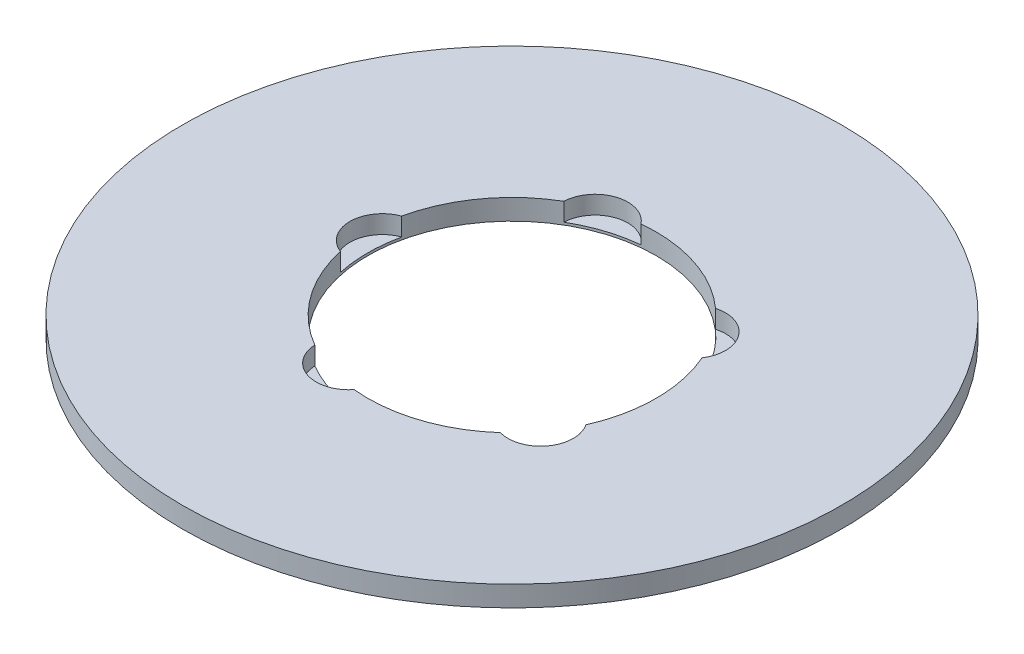
SolidWorks part; units mm, degrees
ref_plane "Front Plane" through (0, 0, 0) normal (0, 0, 1) x (1, 0, 0)
ref_plane "Top Plane" through (0, 0, 0) normal (0, 1, 0) x (1, 0, 0)
ref_plane "Right Plane" through (0, 0, 0) normal (1, 0, 0) x (0, 0, -1)
sketch "Sketch1" plane through (0, 0, 0) normal (0, 1, 0) x (1, 0, 0)
  circle A0 centre (0, 0) radius 80
  dimension "FLANGE_OD" = 160
extrude "Boss-Extrude1" add sketch "Sketch1" along normal blind 5
sketch "Sketch2" plane through (0, 0, 0) normal (0, 1, 0) x (1, 0, 0)
  circle A0 centre (0, 0) radius 35
  dimension "BORE_D" = 70
extrude "Cut-Extrude1" cut sketch "Sketch2" along normal through all
sketch "Sketch3" plane through (0, 5, 0) normal (0, 1, 0) x (1, 0, 0)
  circle A0 centre (0, 0) radius 31.4431 construction
  circle A1 centre (-31.4431, 0) radius 7.9271
  dimension "BOLT_D" = 15.8541
  dimension "BOLT_PCD" = 62.8863
extrude "Cut-Extrude2" cut sketch "Sketch3" against normal blind 4.3915
pattern_circular "CirPattern1" count 5 over 360 about axis through (0, 0, 0) along (0, 1, 0) of "Cut-Extrude2"
